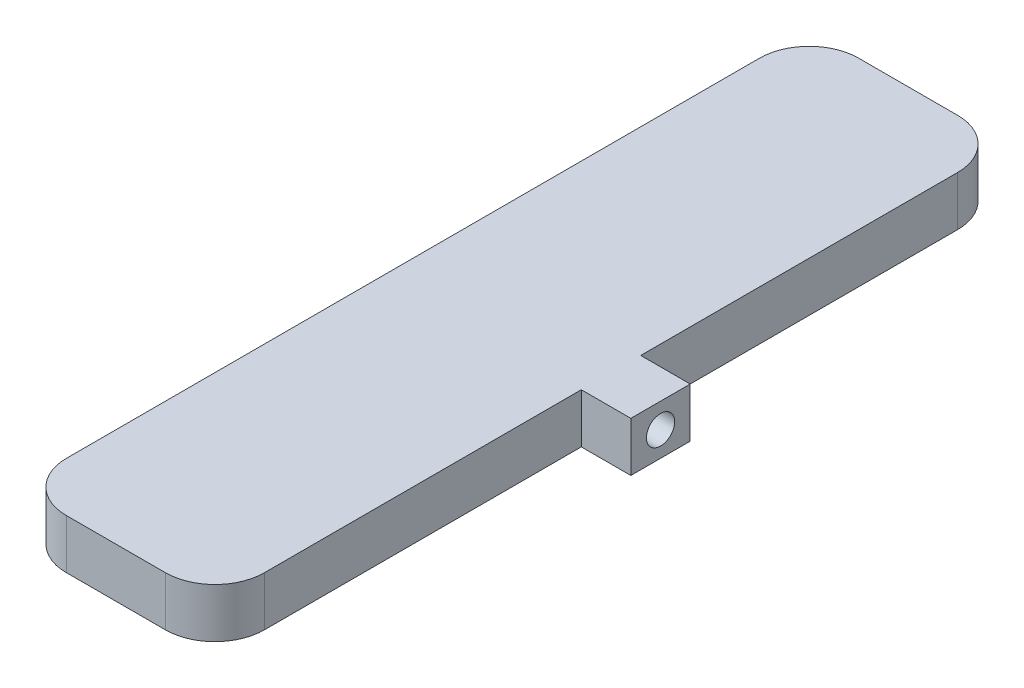
SolidWorks part; units mm, degrees
ref_plane "Front Plane" through (0, 0, 0) normal (0, 0, 1) x (1, 0, 0)
ref_plane "Top Plane" through (0, 0, 0) normal (0, 1, 0) x (1, 0, 0)
ref_plane "Right Plane" through (0, 0, 0) normal (1, 0, 0) x (0, 0, -1)
sketch "Sketch1" plane through (0, 0, 0) normal (0, 1, 0) x (1, 0, 0)
  line L1 (-10, 40) -> (10, 40)
  line L2 (-10, 40) -> (-10, -40)
  line L3 (-10, -40) -> (10, -40)
  line L4 (10, 40) -> (10, -40)
  line L5 (-10, 40) -> (10, -40) construction
  line L6 (-10, -40) -> (10, 40) construction
  point P0 (0, 0)
  dimension "D1" = 20
  dimension "D2" = 80
extrude "Boss-Extrude1" add sketch "Sketch1" along normal blind 5
fillet "Fillet1" radius 5 4 edges at (-10, 2.5, -40) (10, 2.5, -40) (-10, 2.5, 40) (10, 2.5, 40)
shell "Shell1" thickness 2 removed face at (0, 0, 0)
sketch "Sketch2" plane through (10, 0, 0) normal (1, 0, 0) x (0, 0, -1)
  line L0 (-35, 0) -> (35, 0) construction
  line L1 (-3, 0) -> (3, 0)
  line L2 (-3, 0) -> (-3, 5)
  line L3 (-3, 5) -> (3, 5)
  line L4 (3, 0) -> (3, 5)
  line L5 (-35, 5) -> (35, 5) construction
  point P8 (0, 5)
  point P9 (0, 0)
  dimension "D1" = 6
extrude "Boss-Extrude2" add sketch "Sketch2" along normal blind 5
sketch "Sketch3" plane through (15, 0, 0) normal (1, 0, 0) x (0, 0, -1)
  line L0 (-3, 0) -> (3, 0) construction
  line L1 (-3, 5) -> (-3, 0) construction
  circle A0 centre (0, 2.5) radius 1.425
  point P2 (0, 0)
  point P5 (0, 0)
  point P8 (-3, 2.5)
  dimension "D1" = 2.85
extrude "Cut-Extrude1" cut sketch "Sketch3" against normal blind 4
